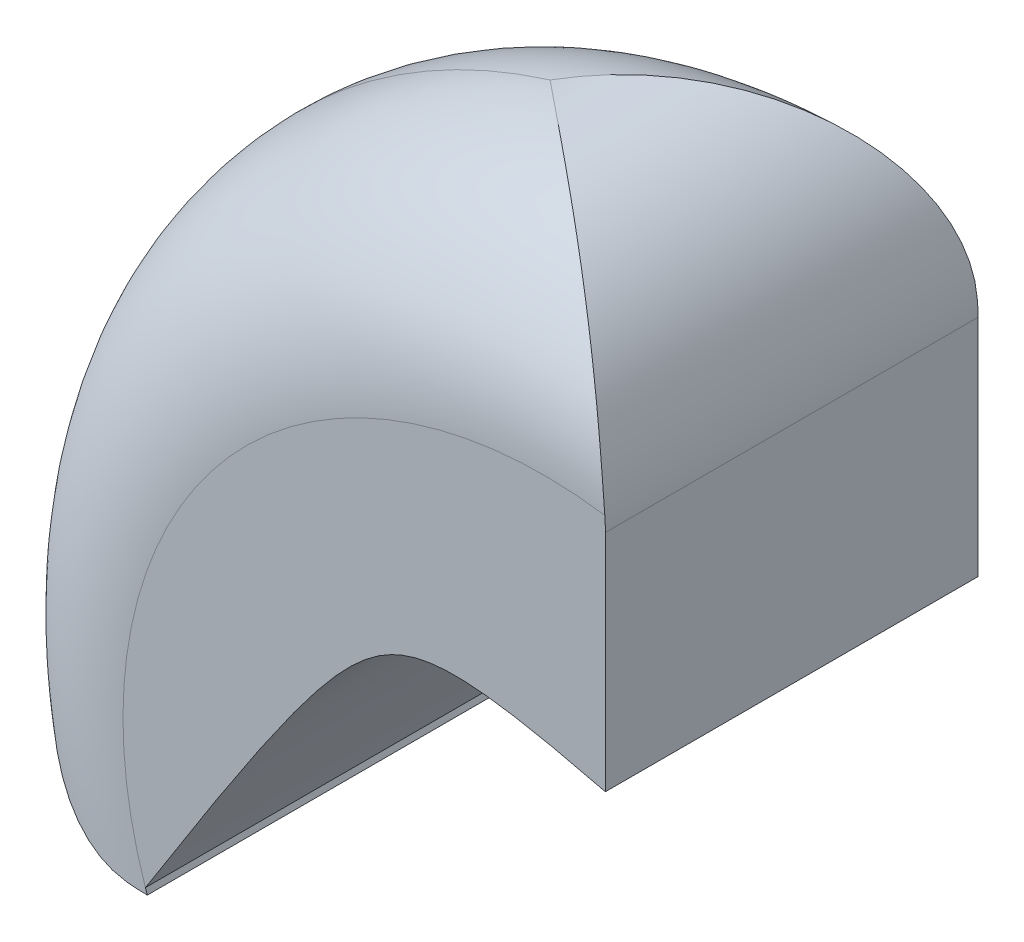
SolidWorks part; units mm, degrees
ref_plane "Front Plane" through (0, 0, 0) normal (0, 0, 1) x (1, 0, 0)
ref_plane "Top Plane" through (0, 0, 0) normal (0, 1, 0) x (1, 0, 0)
ref_plane "Right Plane" through (0, 0, 0) normal (1, 0, 0) x (0, 0, -1)
sketch "Sketch2" plane through (0, 0, 0) normal (0, 0, 1) x (1, 0, 0)
  line L0 (0, 0) -> (-8.89, 0)
  line L1 (0, 0) -> (0, 10.16)
  arc A0 (-8.89, 0) -> (0, 10.16) centre (-0.837, 1.923) cw
  dimension "D1" = 10.16
  dimension "D2" = 8.89
extrude "Boss-Extrude1" add sketch "Sketch2" along normal blind 5.08
fillet "Fillet1" radius 2.54 4 edges at (0, 10.16, 2.54) (-7.0679, 7.375, 5.08) (-8.89, 0, 2.54) (-7.0679, 7.375, 0)
sketch "Sketch4" plane through (0, 0, 0) normal (0, 0, 1) x (1, 0, 0)
  line L0 (0, -3.0174) -> (0, 3.0174) construction
  line L1 (0, 4.3425) -> (0, 0)
  line L2 (0, 0) -> (-6.2447, 0)
  line L3 (-6.2447, 0) -> (-6.2708, 0.0751)
  arc A0 (-0.0077, 7.6022) -> (-6.2447, 0) centre (-0.837, 1.923) ccw construction
  conic Q0 (-6.2708, 0.0751) -> (0, 4.3425) control (-3.1058, 5.1134) rho 0.75
extrude "Cut-Extrude1" cut sketch "Sketch4" along normal blind 5.08 contours Q0 L1 L2 L3
scale "Scale1" scale about origin uniform scaling yes scale factor 0.8
